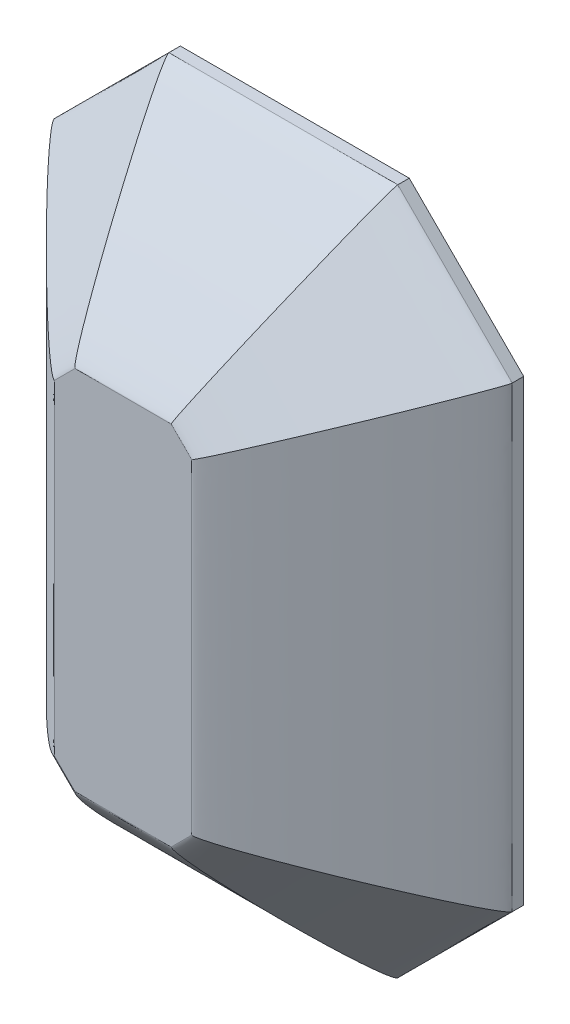
SolidWorks part; units mm, degrees
ref_plane "Front Plane" through (0, 0, 0) normal (1, 0, 0) x (0, 1, 0)
ref_plane "Top Plane" through (0, 0, 0) normal (0, 0, 1) x (0, 1, 0)
ref_plane "Right Plane" through (0, 0, 0) normal (0, 1, 0) x (-1, 0, 0)
sketch "Sketch1" plane through (0, 0, 0) normal (0, 0, 1) x (0, 1, 0)
  line L0 (-400, 0) -> (-499.9648, 99.9648)
  line L1 (0, 0) -> (-400, 0)
  line L2 (0, 0) -> (0, 400)
  line L3 (0, 400) -> (-400, 400)
  line L4 (-400, 0) -> (-400, 400)
  line L5 (-499.9648, 99.9648) -> (-499.9648, 299.9149)
  line L6 (-499.9648, 299.9149) -> (-400, 400)
  line L7 (0, 0) -> (99.9648, 99.9648)
  line L8 (99.9648, 99.9648) -> (99.9648, 299.9149)
  line L9 (99.9648, 299.9149) -> (0, 400)
  point P5 (0, 0)
  point P10 (0, 0)
  dimension "D1" = 400
  dimension "D2" = 400
extrude "Boss-Extrude2" add sketch "Sketch1" along normal blind 150 contours L0 L5 L6 L3 L9 L8 L7 L1
fillet "Fillet1" radius 140 8 edges at (-49.9824, -449.9824, 150) (-199.9398, -499.9648, 150) (-349.9574, -449.9824, 150) (-400, -200, 150) (-349.9574, 49.9824, 150) (-199.9398, 99.9648, 150) (-49.9824, 49.9824, 150) (0, -200, 150) conic rho 0.05
